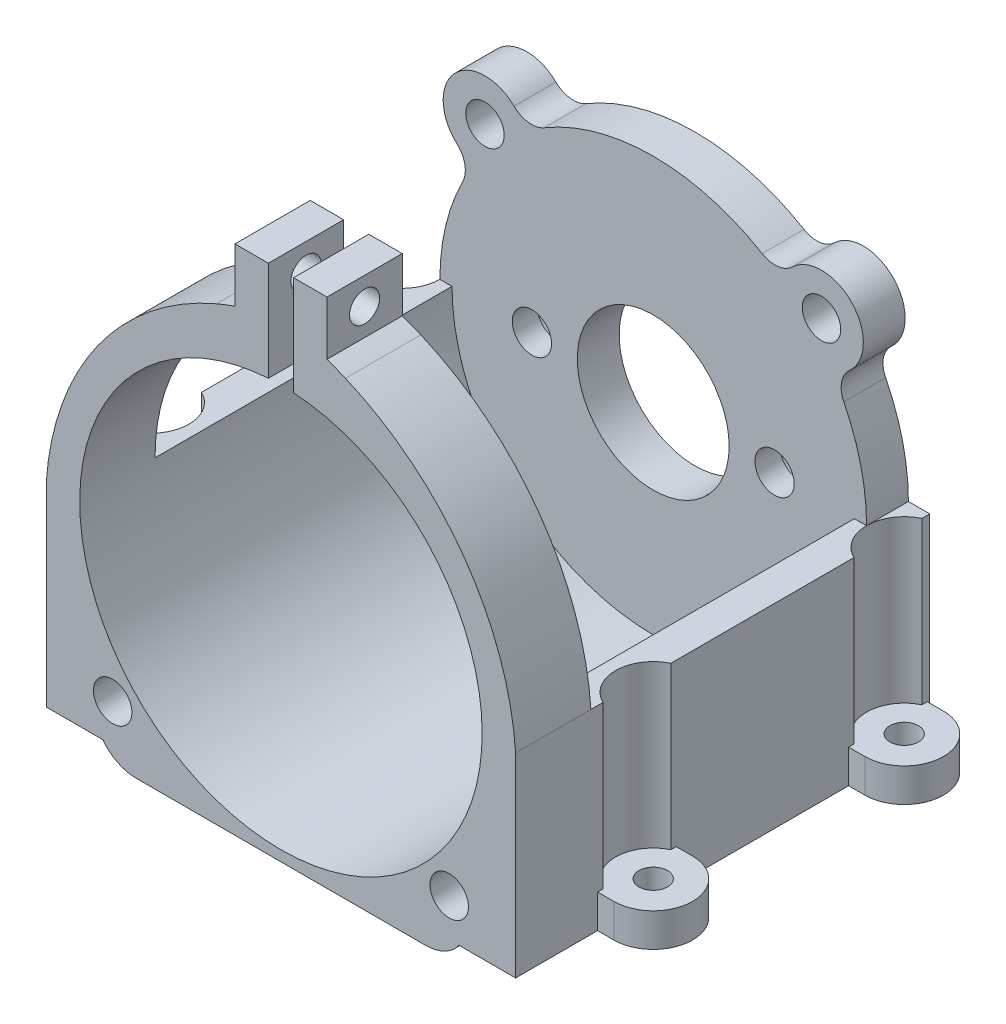
SolidWorks part; units mm, degrees
ref_plane "Спереди" through (0, 0, 0) normal (0, 0, 1) x (1, 0, 0)
ref_plane "Сверху" through (0, 0, 0) normal (0, 1, 0) x (1, 0, 0)
ref_plane "Справа" through (0, 0, 0) normal (1, 0, 0) x (0, 0, -1)
sketch "Эскиз1" plane through (0, 0, 0) normal (0, 0, 1) x (1, 0, 0)
  line L0 (0, 0) -> (-14.5, 0) construction
  line L1 (0, 0) -> (14.5, 0) construction
  line L2 (0, 0) -> (0, 14.5) construction
  line L3 (0, 0) -> (0, -14.5) construction
  circle A1 centre (-14.5, 0) radius 2.35
  circle A2 centre (14.5, 0) radius 2.35
  circle A3 centre (0, 0) radius 9.075
  circle A4 centre (0, 14.5) radius 1.75 construction
  circle A5 centre (0, -14.5) radius 1.75 construction
  arc A70 (-13.0191, -21.9261) -> (-16.6363, -22.3491) centre (-14.5508, -24.5056) ccw
  arc A71 (-13.0191, -21.9261) -> (13.0191, -21.9261) centre (0, 0) ccw
  arc A72 (16.6363, -22.3491) -> (13.0191, -21.9261) centre (14.5508, -24.5056) ccw
  arc A73 (16.6363, -22.3491) -> (23.4552, -15.0368) centre (20.1122, -18.755) ccw
  arc A74 (22.7808, -11.4579) -> (23.4552, -15.0368) centre (25.4609, -12.8059) ccw
  arc A75 (22.7808, -11.4579) -> (22.7808, 11.4579) centre (0, 0) ccw
  arc A76 (23.4552, 15.0368) -> (22.7808, 11.4579) centre (25.4609, 12.8059) ccw
  arc A77 (23.4552, 15.0368) -> (16.6363, 22.3491) centre (20.1122, 18.755) ccw
  arc A78 (13.0191, 21.9261) -> (16.6363, 22.3491) centre (14.5508, 24.5056) ccw
  arc A79 (13.0191, 21.9261) -> (-13.0191, 21.9261) centre (0, 0) ccw
  arc A80 (-16.6363, 22.3491) -> (-13.0191, 21.9261) centre (-14.5508, 24.5056) ccw
  arc A81 (-16.6363, 22.3491) -> (-23.4552, 15.0368) centre (-20.1122, 18.755) ccw
  arc A82 (-22.7808, 11.4579) -> (-23.4552, 15.0368) centre (-25.4609, 12.8059) ccw
  arc A83 (-22.7808, 11.4579) -> (-22.7808, -11.4579) centre (0, 0) ccw
  arc A84 (-23.4552, -15.0368) -> (-22.7808, -11.4579) centre (-25.4609, -12.8059) ccw
  arc A85 (-23.4552, -15.0368) -> (-16.6363, -22.3491) centre (-20.1122, -18.755) ccw
  dimension "D2" = 4.7
  dimension "D3" = 14.5
  dimension "D4" = 18.15
  dimension "D5" = 3.5
  dimension "D1" = 14.5
extrude "Бобышка-Вытянуть1" add sketch "Эскиз1" along normal blind 5
sketch "Эскиз2" plane through (0, 0, 5) normal (0, 0, 1) x (1, 0, 0)
  line L0 (-25.3, 0) -> (-21.3, 0)
  line L1 (21.3, 0) -> (25.3, 0)
  line L2 (0, -28.25) -> (0, -23.25) construction
  line L3 (0, -23.25) -> (16.0468, -23.25) construction
  line L4 (35.3, -23.25) -> (50, -23.25)
  line L5 (-35.3, -23.25) -> (-50, -23.25)
  line L6 (-25.3, 0) -> (-25.3, -13.25)
  line L7 (25.3, 0) -> (25.3, -13.25)
  line L8 (-50, -23.25) -> (-50, -28.25)
  line L9 (-50, -28.25) -> (50, -28.25)
  line L10 (50, -28.25) -> (50, -23.25)
  arc A0 (-21.3, 0) -> (21.3, 0) centre (0, 0) ccw
  arc A2 (35.3, -23.25) -> (25.3, -13.25) centre (35.3, -13.25) cw
  arc A3 (-25.3, -13.25) -> (-35.3, -23.25) centre (-35.3, -13.25) cw
  dimension "D1" = 10
  dimension "D6" = 21.3
  dimension "D2" = 5
  dimension "D3" = 100
  dimension "D4" = 5
  dimension "D5" = 4
extrude "Бобышка-Вытянуть2" add sketch "Эскиз2" along normal blind 44.5 and the other way blind 5
sketch "Эскиз4" plane through (0, 0, 49.5) normal (0, 0, 1) x (1, 0, 0)
  line L0 (0, 0) -> (0, 30) construction
  line L1 (21.3, 0) -> (25.3, 0)
  line L2 (-25.3, 0) -> (-21.3, 0)
  line L3 (0, 30) -> (-1.5, 30) construction
  line L4 (0, 30) -> (1.5, 30) construction
  line L5 (-1.5, 29.9162) -> (-1.5, 21.2471)
  line L6 (1.5, 29.9162) -> (1.5, 21.2471)
  line L7 (-1.5, 29.9162) -> (-1.5, 35.9162)
  line L8 (-1.5, 35.9162) -> (-5.5, 35.9162)
  line L9 (-5.5, 35.9162) -> (-5.5, 29.4654)
  line L10 (1.5, 29.9162) -> (1.5, 35.9162)
  line L11 (1.5, 35.9162) -> (5.5, 35.9162)
  line L12 (5.5, 35.9162) -> (5.5, 29.4654)
  arc A0 (21.3, 0) -> (1.5, 21.2471) centre (0, 0) ccw
  arc A1 (-5.5, 29.4654) -> (-25.3, 0) centre (3.9362, 1.7393) ccw
  arc A2 (5.5, 29.4654) -> (25.3, 0) centre (-3.9362, 1.7393) cw
  arc A3 (-1.5, 21.2471) -> (-21.3, 0) centre (0, 0) ccw
  dimension "D1" = 30
  dimension "D2" = 1.5
  dimension "D3" = 6
  dimension "D4" = 4
extrude "Бобышка-Вытянуть3" add sketch "Эскиз4" against normal blind 9
sketch "Эскиз5" plane through (-5.5, 0, 0) normal (-1, 0, 0) x (0, 0, 1)
  line L0 (45, 35.9162) -> (45, 29.4654) construction
  line L1 (40.5, 35.9162) -> (49.5, 35.9162) construction
  line L2 (40.5, 29.4654) -> (49.5, 29.4654) construction
  circle A0 centre (45, 32.6908) radius 1.8
  dimension "D1" = 3.6
extrude "Вырез-Вытянуть2" cut sketch "Эскиз5" against normal blind 19
sketch "Эскиз9" plane through (0, -23.25, 0) normal (0, 1, 0) x (1, 0, 0)
  line L0 (25.3, 0) -> (25.3, -49.5)
  line L1 (-25.3, 0) -> (25.3, 0)
  line L2 (-25.3, 0) -> (-25.3, -49.5)
  line L3 (-25.3, -49.5) -> (25.3, -49.5)
  line L5 (-59.8904, -57.7314) -> (58.8188, -57.7314)
  line L6 (-59.8904, -57.7314) -> (-59.8904, 10.3746)
  line L7 (-59.8904, 10.3746) -> (58.8188, 10.3746)
  line L8 (58.8188, -57.7314) -> (58.8188, 10.3746)
  line L9 (25.3, -49.5) -> (35.3, -49.5) construction
extrude "Вырез-Вытянуть5" cut sketch "Эскиз9" against normal blind 10 and the other way blind 10
sketch "Эскиз10" plane through (0, 0, 49.5) normal (0, 0, 1) x (1, 0, 0)
  line L0 (0, -21.3) -> (0, -23.3) construction
  line L1 (-25.3, -28.25) -> (-25.3, -23.3)
  line L2 (-25.3, 0) -> (-25.3, -28.25) construction
  line L3 (-25.3, -23.3) -> (25.3, -23.3)
  line L4 (25.3, -28.25) -> (25.3, 0) construction
  line L5 (25.3, -23.3) -> (25.3, -28.25)
  line L6 (25.3, -28.25) -> (-25.3, -28.25)
  arc A0 (-1.5, 21.2471) -> (1.5, 21.2471) centre (0, 0) ccw construction
  dimension "D1" = 2
extrude "Вырез-Вытянуть6" cut sketch "Эскиз10" against normal through all
sketch "Эскиз11" plane through (0, 0, 0) normal (0, 0, -1) x (-1, 0, 0)
  circle A1 centre (-20.1122, -18.755) radius 2.3
  circle A2 centre (20.1122, -18.755) radius 2.3
  dimension "D1" = 4.6
extrude "Вырез-Вытянуть7" cut sketch "Эскиз11" against normal through all
sketch "Эскиз12" plane through (0, 0, 0) normal (0, 0, -1) x (-1, 0, 0)
  circle A0 centre (-20.1122, 18.755) radius 2.3
  circle A1 centre (20.1122, 18.755) radius 2.3
  dimension "D1" = 4.6
extrude "Вырез-Вытянуть8" cut sketch "Эскиз12" against normal blind 10
sketch "Эскиз13" plane through (0, 0, 0) normal (0, 0, -1) x (-1, 0, 0)
  circle A0 centre (-14.5, 0) radius 4.5
  circle A1 centre (14.5, 0) radius 4.5
  dimension "D1" = 9
extrude "Вырез-Вытянуть9" cut sketch "Эскиз13" against normal blind 2
sketch "Эскиз14" plane through (0, -23.3, 0) normal (0, -1, 0) x (1, 0, 0)
  line L0 (0, 0) -> (0, 35) construction
  line L1 (0, 35) -> (-30, 35) construction
  line L2 (-30, 39.7) -> (-25.3, 39.7)
  line L3 (-25.3, 0) -> (-25.3, 49.5) construction
  line L4 (-30, 30.3) -> (-25.3, 30.3)
  line L5 (-25.3, 39.7) -> (-25.3, 30.3)
  line L6 (25.3, 39.7) -> (25.3, 30.3)
  line L7 (30, 30.3) -> (25.3, 30.3)
  line L8 (30, 39.7) -> (25.3, 39.7)
  line L9 (0, 20) -> (-25.3, 20) construction
  line L10 (30, 0.3) -> (25.3, 0.3)
  line L11 (30, 9.7) -> (25.3, 9.7)
  line L12 (25.3, 0.3) -> (25.3, 9.7)
  line L13 (-25.3, 0.3) -> (-25.3, 9.7)
  line L14 (-30, 9.7) -> (-25.3, 9.7)
  line L15 (-30, 0.3) -> (-25.3, 0.3)
  line L17 (25.3, 0) -> (-25.3, 0) construction
  circle A0 centre (-30, 35) radius 1.7
  arc A1 (-30, 39.7) -> (-30, 30.3) centre (-30, 35) ccw
  arc A2 (30, 39.7) -> (30, 30.3) centre (30, 35) cw
  circle A3 centre (30, 35) radius 1.7
  circle A4 centre (30, 5) radius 1.7
  arc A5 (30, 0.3) -> (30, 9.7) centre (30, 5) ccw
  arc A6 (-30, 0.3) -> (-30, 9.7) centre (-30, 5) cw
  circle A7 centre (-30, 5) radius 1.7
  dimension "D1" = 3.4
  dimension "D2" = 3
  dimension "D3" = 35
  dimension "D4" = 30
  dimension "D5" = 20
extrude "Бобышка-Вытянуть4" add sketch "Эскиз14" against normal blind 4
sketch "Эскиз15" plane through (0, 0, 49.5) normal (0, 0, 1) x (1, 0, 0)
  circle A0 centre (0, 0) radius 24.05
  dimension "D1" = 48.1
extrude "Вырез-Вытянуть10" cut sketch "Эскиз15" against normal up to surface (44.5 mm away) up to face at (22.4122, 18.755, 5)
sketch "Эскиз17" plane through (0, 0, 49.5) normal (0, 0, 1) x (1, 0, 0)
  line L1 (24.05, 0) -> (28.05, 0)
  line L2 (28.05, 0) -> (28.05, -23.3)
  line L4 (21.3, -23.3) -> (21.3, -25.3)
  line L5 (25.3, -23.3) -> (5.9592, -23.3) construction
  line L10 (-21.3, -25.3) -> (21.3, -25.3)
  line L11 (-5.9592, -23.3) -> (-25.3, -23.3) construction
  line L12 (21.3, -23.3) -> (28.05, -23.3)
  line L13 (30, -23.3) -> (25.3, -23.3) construction
  line L14 (25.3, -23.3) -> (25.3, 0) construction
  line L15 (0, 0) -> (0, -30.9745) construction
  line L16 (-21.3, -23.3) -> (-28.05, -23.3)
  line L17 (-21.3, -23.3) -> (-21.3, -25.3)
  line L18 (-28.05, 0) -> (-28.05, -23.3)
  line L19 (-24.05, 0) -> (-28.05, 0)
  arc A2 (-24.05, 0) -> (24.05, 0) centre (0, 0) ccw
  circle A4 centre (20.1122, -18.755) radius 2.3
  circle A5 centre (-20.1122, -18.755) radius 2.3
  point P26 (0, -25.3)
  dimension "D1" = 2
  dimension "D2" = 4
  dimension "D3" = 24.05
  dimension "D4" = 4
extrude "Бобышка-Вытянуть5" add sketch "Эскиз17" against normal up to surface (49.5 mm away) up to face at (10, 0, 0)
sketch "Эскиз18" plane through (0, 0, 49.5) normal (0, 0, 1) x (1, 0, 0)
  line L0 (-24.05, 0) -> (-28.05, 0)
  line L1 (-5.5, 29.4654) -> (-1.5, 24.0032)
  line L2 (0, 0) -> (0, 53.9998) construction
  line L3 (5.5, 29.4654) -> (1.5, 24.0032)
  line L4 (24.05, 0) -> (28.05, 0)
  arc A0 (-28.05, 0) -> (-5.5, 29.4654) centre (5.5031, -2.3168) cw
  arc A1 (-24.05, 0) -> (-1.5, 24.0032) centre (0, 0) cw
  arc A2 (24.05, 0) -> (1.5, 24.0032) centre (0, 0) ccw
  arc A3 (28.05, 0) -> (5.5, 29.4654) centre (-5.5031, -2.3168) ccw
  point P16 (0, 0)
extrude "Бобышка-Вытянуть6" add sketch "Эскиз18" against normal up to surface (9 mm away) up to face at (-12.1794, 22.1847, 40.5)
sketch "Эскиз19" plane through (0, -19.3, 0) normal (0, 1, 0) x (1, 0, 0)
  circle A0 centre (30, -5) radius 4.5
  circle A1 centre (30, -35) radius 4.5
  circle A2 centre (-30, -35) radius 4.5
  circle A3 centre (-30, -5) radius 4.5
  dimension "D1" = 9
extrude "Вырез-Вытянуть11" cut sketch "Эскиз19" along normal through all
sketch "Эскиз20" plane through (0, 0, 5) normal (0, 0, 1) x (1, 0, 0)
  line L0 (-14.9818, -18.8135) -> (15.8986, -18.0454)
  arc A0 (-14.9818, -18.8135) -> (15.8986, -18.0454) centre (0, 0) ccw
extrude "Бобышка-Вытянуть7" add sketch "Эскиз20" against normal up to surface (5 mm away) up to face at (0, -23.675, 0)
fillet "Скругление2" radius 5 2 edges at (21.3, -25.3, 24.75) (-21.3, -25.3, 24.75)
